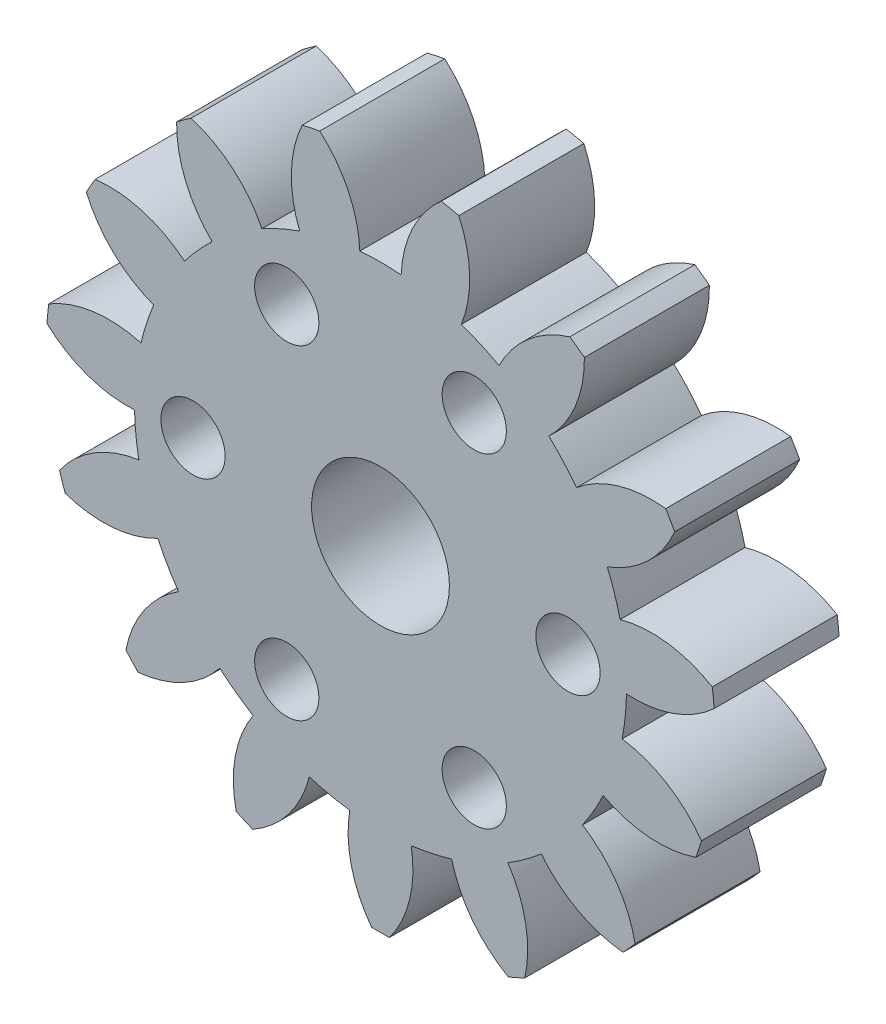
SolidWorks part; units mm, degrees
material "6061 Alloy"
ref_plane "Front Plane" through (0, 0, 0) normal (0, 0, 1) x (1, 0, 0)
ref_plane "Top Plane" through (0, 0, 0) normal (0, 1, 0) x (1, 0, 0)
ref_plane "Right Plane" through (0, 0, 0) normal (1, 0, 0) x (0, 0, -1)
ref_axis "Axis1" through (0, -55, 0) along (0, 1, 0)
sketch "Model" plane through (0, 0, 0) normal (0, 0, 1) x (1, 0, 0)
  circle A0 centre (-4.7625, -8.2489) radius 1.632
  circle A1 centre (4.7625, -8.2489) radius 1.632
  circle A2 centre (9.525, 0) radius 1.632
  circle A3 centre (4.7625, 8.2489) radius 1.632
  circle A4 centre (-4.7625, 8.2489) radius 1.632
  circle A5 centre (-9.525, 0) radius 1.632
  circle A6 centre (0, 0) radius 3.5
  arc A7 (-16.9485, 1.3222) -> (-12.4963, -0.2576) centre (-12.878, 5.7303) ccw
  arc A8 (-12.4963, -0.2576) -> (-12.2768, -2.3462) centre (0, 0) ccw
  arc A9 (-12.2768, -2.3462) -> (-16.3032, -4.8171) centre (-11.4052, -8.2825) ccw
  arc A10 (-16.3032, -4.8171) -> (-16.021, -5.6857) centre (0, 0) ccw
  arc A11 (-16.021, -5.6857) -> (-11.3112, -5.318) centre (-14.0954, -0.0031) ccw
  arc A12 (-11.3112, -5.318) -> (-10.2612, -7.1368) centre (0, 0) ccw
  arc A13 (-10.2612, -7.1368) -> (-12.9345, -11.0317) centre (-7.0504, -12.2054) ccw
  arc A14 (-12.9345, -11.0317) -> (-12.3233, -11.7105) centre (0, 0) ccw
  arc A15 (-12.3233, -11.7105) -> (-8.1703, -9.4589) centre (-12.8755, -5.736) ccw
  arc A16 (-8.1703, -9.4589) -> (-6.4712, -10.6934) centre (0, 0) ccw
  arc A17 (-6.4712, -10.6934) -> (-7.3292, -15.3389) centre (-1.4765, -14.0178) ccw
  arc A18 (-7.3292, -15.3389) -> (-6.4948, -15.7104) centre (0, 0) ccw
  arc A19 (-6.4948, -15.7104) -> (-3.6166, -11.9643) centre (-9.4293, -10.477) ccw
  arc A20 (-3.6166, -11.9643) -> (-1.5624, -12.401) centre (0, 0) ccw
  arc A21 (-1.5624, -12.401) -> (-0.4567, -16.9939) centre (4.3528, -13.4065) ccw
  arc A22 (-0.4567, -16.9939) -> (0.4567, -16.9939) centre (0, 0) ccw
  arc A23 (0.4567, -16.9939) -> (1.5624, -12.401) centre (-4.3528, -13.4065) ccw
  arc A24 (1.5624, -12.401) -> (3.6166, -11.9643) centre (0, 0) ccw
  arc A25 (3.6166, -11.9643) -> (6.4948, -15.7104) centre (9.4293, -10.477) ccw
  arc A26 (6.4948, -15.7104) -> (7.3292, -15.3389) centre (0, 0) ccw
  arc A27 (7.3292, -15.3389) -> (6.4712, -10.6934) centre (1.4765, -14.0178) ccw
  arc A28 (6.4712, -10.6934) -> (8.1703, -9.4589) centre (0, 0) ccw
  arc A29 (8.1703, -9.4589) -> (12.3233, -11.7105) centre (12.8755, -5.736) ccw
  arc A30 (12.3233, -11.7105) -> (12.9345, -11.0317) centre (0, 0) ccw
  arc A31 (12.9345, -11.0317) -> (10.2612, -7.1368) centre (7.0504, -12.2054) ccw
  arc A32 (10.2612, -7.1368) -> (11.3112, -5.318) centre (0, 0) ccw
  arc A33 (11.3112, -5.318) -> (16.021, -5.6857) centre (14.0954, -0.0031) ccw
  arc A34 (16.021, -5.6857) -> (16.3032, -4.8171) centre (0, 0) ccw
  arc A35 (16.3032, -4.8171) -> (12.2768, -2.3462) centre (11.4052, -8.2825) ccw
  arc A36 (12.2768, -2.3462) -> (12.4963, -0.2576) centre (0, 0) ccw
  arc A37 (12.4963, -0.2576) -> (16.9485, 1.3222) centre (12.878, 5.7303) ccw
  arc A38 (16.9485, 1.3222) -> (16.853, 2.2305) centre (0, 0) ccw
  arc A39 (16.853, 2.2305) -> (12.1697, 2.8501) centre (13.788, -2.9276) ccw
  arc A40 (12.1697, 2.8501) -> (11.5207, 4.8474) centre (0, 0) ccw
  arc A41 (11.5207, 4.8474) -> (14.9455, 8.1014) centre (9.434, 10.4728) ccw
  arc A42 (14.9455, 8.1014) -> (14.4888, 8.8924) centre (0, 0) ccw
  arc A43 (14.4888, 8.8924) -> (9.9584, 7.5536) centre (13.7867, 2.9336) ccw
  arc A44 (9.9584, 7.5536) -> (8.5531, 9.1142) centre (0, 0) ccw
  arc A45 (8.5531, 9.1142) -> (10.3582, 13.4799) centre (4.3587, 13.4045) ccw
  arc A46 (10.3582, 13.4799) -> (9.6193, 14.0168) centre (0, 0) ccw
  arc A47 (9.6193, 14.0168) -> (6.0251, 10.9509) centre (11.4016, 8.2876) ccw
  arc A48 (6.0251, 10.9509) -> (4.1066, 11.8051) centre (0, 0) ccw
  arc A49 (4.1066, 11.8051) -> (3.9799, 16.5276) centre (-1.4703, 14.0185) ccw
  arc A50 (3.9799, 16.5276) -> (3.0865, 16.7175) centre (0, 0) ccw
  arc A51 (3.0865, 16.7175) -> (1.0501, 12.4548) centre (7.045, 12.2085) ccw
  arc A52 (1.0501, 12.4548) -> (-1.0501, 12.4548) centre (0, 0) ccw
  arc A53 (-1.0501, 12.4548) -> (-3.0865, 16.7175) centre (-7.045, 12.2085) ccw
  arc A54 (-3.0865, 16.7175) -> (-3.9799, 16.5276) centre (0, 0) ccw
  arc A55 (-3.9799, 16.5276) -> (-4.1066, 11.8051) centre (1.4703, 14.0185) ccw
  arc A56 (-4.1066, 11.8051) -> (-6.0251, 10.9509) centre (0, 0) ccw
  arc A57 (-6.0251, 10.9509) -> (-9.6193, 14.0168) centre (-11.4016, 8.2876) ccw
  arc A58 (-9.6193, 14.0168) -> (-10.3582, 13.4799) centre (0, 0) ccw
  arc A59 (-10.3582, 13.4799) -> (-8.5531, 9.1142) centre (-4.3587, 13.4045) ccw
  arc A60 (-8.5531, 9.1142) -> (-9.9584, 7.5536) centre (0, 0) ccw
  arc A61 (-9.9584, 7.5536) -> (-14.4888, 8.8924) centre (-13.7867, 2.9336) ccw
  arc A62 (-14.4888, 8.8924) -> (-14.9455, 8.1014) centre (0, 0) ccw
  arc A63 (-14.9455, 8.1014) -> (-11.5207, 4.8474) centre (-9.434, 10.4728) ccw
  arc A64 (-11.5207, 4.8474) -> (-12.1697, 2.8501) centre (0, 0) ccw
  arc A65 (-12.1697, 2.8501) -> (-16.853, 2.2305) centre (-13.788, -2.9276) ccw
  arc A66 (-16.853, 2.2305) -> (-16.9485, 1.3222) centre (0, 0) ccw
extrude "Boss-Extrude1" add sketch "Model" along normal blind 6.35
